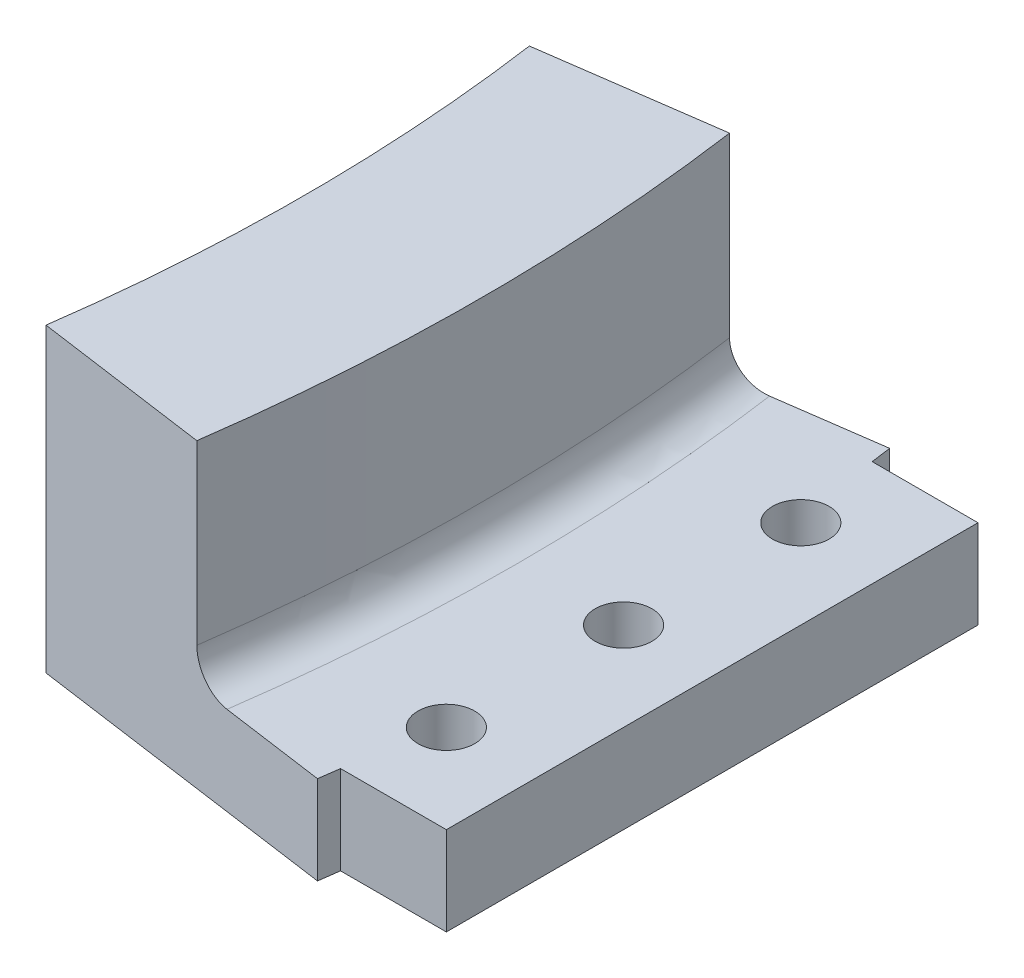
SolidWorks part; units mm, degrees
ref_plane "Front Plane" through (0, 0, 0) normal (0, 0, 1) x (1, 0, 0)
ref_plane "Top Plane" through (0, 0, 0) normal (0, 1, 0) x (1, 0, 0)
ref_plane "Right Plane" through (0, 0, 0) normal (1, 0, 0) x (0, 0, -1)
ref_axis "Axis1" through (0, -55, 0) along (0, 1, 0)
ref_axis "Axis2" through (0, 0, 71.2617) along (0, 0, -1)
ref_plane "Plane1" through (100, 0, 0) normal (1, 0, 0) x (0, 0, -1)
ref_plane "Plane2" through (111, 0, 0) normal (1, 0, 0) x (0, 0, -1)
sketch "Sketch1" plane through (0, 0, 0) normal (0, 0, 1) x (1, 0, 0)
  line L0 (98, 17) -> (98, 0)
  line L1 (98, 0) -> (116, 0)
  line L2 (116, 0) -> (116, 5)
  line L3 (98, 17) -> (108, 17)
  line L4 (0, -55) -> (0, 55) construction
  line L5 (108, 17) -> (108, 5)
  line L6 (108, 5) -> (116, 5)
  dimension "D1" = 98
  dimension "D2" = 8
  dimension "D3" = 10
  dimension "D5" = 12
  dimension "D7" = 5
revolve "Revolve1" add sketch "Sketch1" angle 16 mid plane about axis through (0, -55, 0) along (0, 1, 0)
sketch "Sketch4" plane through (111, 0, 0) normal (1, 0, 0) x (0, 0, -1)
  line L0 (5, 5) -> (-5, 5)
  line L1 (-5, 5) -> (-5, 0)
  line L6 (-5, 0) -> (5, 0)
  line L7 (5, 0) -> (5, 5)
  line L10 (-16.1441, 0) -> (16.1441, 0) construction
  line L11 (-71.2617, 0) -> (71.2617, 0) construction
  point P5 (0, 0)
  dimension "D1" = 10
  dimension "D4" = 5
extrude "MakerBeamSupport" add sketch "Sketch4" along normal blind 10
sketch "Sketch5" plane through (0, 0, 0) normal (0, -1, 0) x (-1, 0, 0)
  line L2 (-121, 5) -> (-121, -5) construction
  line L3 (-121, 5) -> (-115.8922, 5) construction
  circle A0 centre (-116, 0) radius 1.6
  dimension "D1" = 3.2
  dimension "D2" = 5
  dimension "D3" = 5
extrude "MakerBeamHole" cut sketch "Sketch5" against normal through all
pattern_linear "MakerBeamHoleLinearRight" count 2 spacing 10 along (0, 0, -1) of "MakerBeamSupport", "MakerBeamHole"
mirror "Mirror3" about plane through (0, 0, 0) normal (0, 0, 1) of "MakerBeamHoleLinearRight", "MakerBeamHole"
fillet "Fillet7" radius 2 1 edges at (108, 5, 0)
sketch "Sketch8" plane through (0, 5, 0) normal (0, 1, 0) x (1, 0, 0)
  line L0 (121, 15) -> (121, -15) construction
  line L2 (-9.9, 0) -> (9.9, 0) construction
  circle A0 centre (116, 0) radius 1.6
  dimension "D1" = 3.2
  dimension "D2" = 5
extrude "Cut-Extrude8" cut sketch "Sketch8" against normal through all
